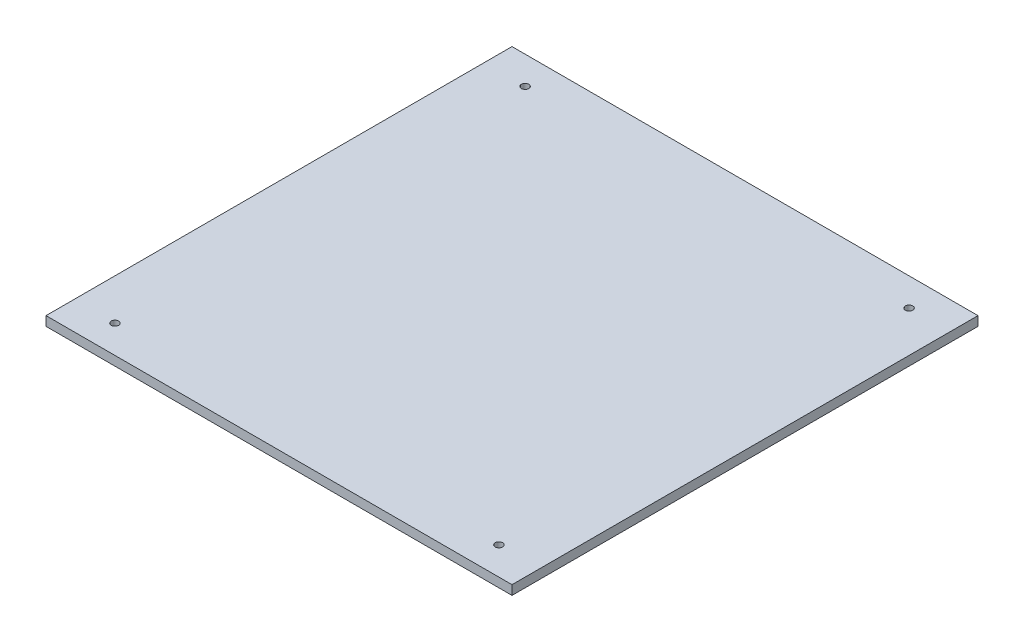
SolidWorks part; units mm, degrees
ref_plane "Front Plane" through (0, 0, 0) normal (0, 0, 1) x (1, 0, 0)
ref_plane "Top Plane" through (0, 0, 0) normal (0, 1, 0) x (1, 0, 0)
ref_plane "Right Plane" through (0, 0, 0) normal (1, 0, 0) x (0, 0, -1)
sketch "Sketch2" plane through (0, 0, 0) normal (0, 1, 0) x (1, 0, 0)
  line L1 (0, 0) -> (250, 0)
  line L2 (0, 0) -> (0, 250)
  line L3 (0, 250) -> (250, 250)
  line L4 (250, 0) -> (250, 250)
  dimension "D1" = 250
  dimension "D2" = 250
extrude "Boss-Extrude1" add sketch "Sketch2" along normal blind 5
sketch "Sketch3" plane through (0, 5, 0) normal (0, 1, 0) x (1, 0, 0)
  circle A0 centre (22, 15) radius 2
extrude "Cut-Extrude1" cut sketch "Sketch3" against normal through all
pattern_linear "LPattern1" count 2 spacing 220 along (0, 0, -1) count 2 spacing 206 along (1, 0, 0) of "Cut-Extrude1"
